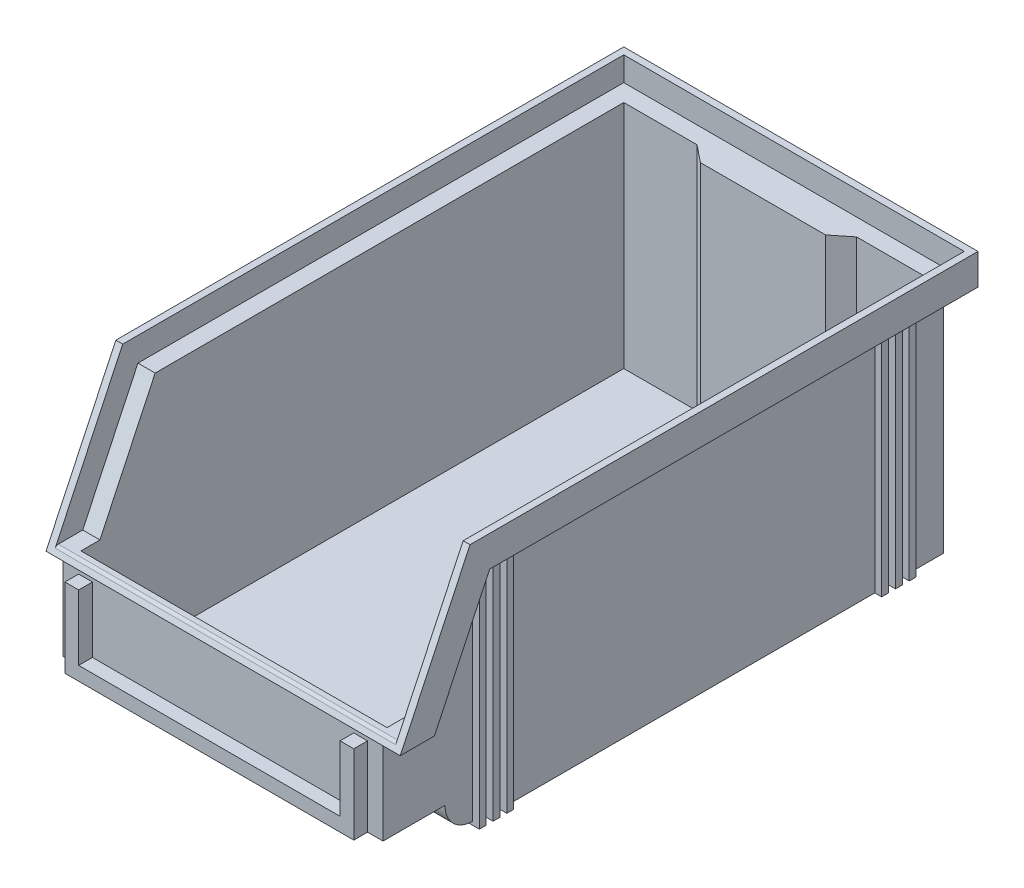
SolidWorks part; units mm, degrees
ref_plane "Front Plane" through (0, 0, 0) normal (0, 0, 1) x (1, 0, 0)
ref_plane "Top Plane" through (0, 0, 0) normal (0, 1, 0) x (1, 0, 0)
ref_plane "Right Plane" through (0, 0, 0) normal (1, 0, 0) x (0, 0, -1)
sketch "Sketch1" plane through (0, 0, 0) normal (0, 1, 0) x (1, 0, 0)
  line L0 (-17.5, 64.5) -> (17.5, 64.5)
  line L1 (-46.5, -68.5) -> (46.5, -68.5)
  line L2 (-46.5, -68.5) -> (-46.5, 68.5)
  line L3 (-46.5, 68.5) -> (46.5, 68.5) construction
  line L4 (46.5, -68.5) -> (46.5, 68.5)
  line L5 (-46.5, -68.5) -> (46.5, 68.5) construction
  line L6 (-46.5, 68.5) -> (46.5, -68.5) construction
  line L7 (-17.5, 64.5) -> (-22.5, 68.5)
  line L8 (17.5, 64.5) -> (22.5, 68.5)
  line L9 (-46.5, 68.5) -> (-22.5, 68.5)
  line L10 (22.5, 68.5) -> (46.5, 68.5)
  point P0 (0, 0)
  point P8 (0, 64.5)
  dimension "D1" = 93
  dimension "D2" = 137
  dimension "D3" = 35
  dimension "D4" = 45
  dimension "D5" = 4
extrude "Boss-Extrude1" add sketch "Sketch1" along normal blind 67
sketch "Sketch2" plane through (0, 67, 0) normal (0, 1, 0) x (1, 0, 0)
  line L0 (-22.5, 68.5) -> (-46.5, 68.5) construction
  line L1 (-51.5, 73.5) -> (51.5, 73.5)
  line L2 (-51.5, 73.5) -> (-51.5, -68.5)
  line L3 (-51.5, -68.5) -> (51.5, -68.5)
  line L4 (51.5, 73.5) -> (51.5, -68.5)
  line L5 (-46.5, 68.5) -> (-46.5, -68.5) construction
  line L6 (46.5, -68.5) -> (46.5, 68.5) construction
  dimension "D1" = 5
  dimension "D2" = 5
  dimension "D3" = 5
extrude "Boss-Extrude2" add sketch "Sketch2" along normal blind 9
sketch "Sketch3" plane through (0, 67, 0) normal (0, -1, 0) x (1, 0, 0)
  line L0 (51.5, -73.5) -> (-51.5, -73.5) construction
  line L2 (45, -73.5) -> (-45, -73.5)
  line L3 (45, -73.5) -> (45, -71.5)
  line L4 (45, -71.5) -> (-45, -71.5)
  line L5 (-45, -73.5) -> (-45, -71.5)
  point P6 (0, -73.5)
  dimension "D1" = 90
  dimension "D2" = 2
extrude "Boss-Extrude3" add sketch "Sketch3" along normal blind 4 contours L3 L2 L5 L4
sketch "Sketch4" plane through (0, 0, 68.5) normal (0, 0, 1) x (1, 0, 0)
  line L0 (-46.5, 67) -> (-46.5, 0) construction
  line L1 (-46.5, 9) -> (46.5, 9)
  line L2 (-46.5, 9) -> (-46.5, 33)
  line L3 (-46.5, 33) -> (46.5, 33)
  line L4 (46.5, 9) -> (46.5, 33)
  line L5 (46.5, 67) -> (46.5, 0) construction
  line L6 (-46.5, 0) -> (46.5, 0) construction
  dimension "D1" = 9
  dimension "D2" = 24
extrude "Boss-Extrude4" add sketch "Sketch4" along normal blind 26
sketch "Sketch5" plane through (-46.5, 0, 0) normal (-1, 0, 0) x (0, 0, 1)
  line L0 (68.5, 67) -> (94.5, 33)
  line L1 (94.5, 33) -> (68.5, 33)
  line L2 (68.5, 33) -> (68.5, 67)
extrude "Boss-Extrude5" add sketch "Sketch5" against normal up to surface (93 mm away) up to face at (46.5, 27.25, 40.75)
sketch "Sketch7" plane through (-51.5, 0, 0) normal (-1, 0, 0) x (0, 0, 1)
  line L0 (68.5, 67) -> (84.5479, 33)
  line L1 (84.5479, 33) -> (94.5, 33)
  line L2 (94.5, 33) -> (74.2042, 76)
  line L3 (74.2042, 76) -> (68.5, 76)
  line L4 (68.5, 76) -> (68.5, 67)
  dimension "D1" = 9
extrude "Boss-Extrude6" add sketch "Sketch7" against normal up to surface (103 mm away) contours L4 L0 L1 L2 L3 up to face at (51.5, 71.5, -2.5)
sketch "Sketch8" plane through (-46.5, 0, 0) normal (-1, 0, 0) x (0, 0, 1)
  line L0 (68.5, 9) -> (68.5, 0) construction
  line L1 (94.5, 9) -> (68.5, 9) construction
  line L2 (76.5, 9) -> (68.5, 9)
  line L3 (68.5, 9) -> (68.5, 1)
  arc A0 (68.5, 1) -> (76.5, 9) centre (68.5, 9) ccw
  dimension "D1" = 8
extrude "Boss-Extrude7" add sketch "Sketch8" against normal up to surface (93 mm away) up to face at (46.5, 27.25, 42.756)
shell "Shell5" thickness 2 removed face at (0, 76, 0.3521)
sketch "Sketch11" plane through (0, 0, 94.5) normal (0, 0, 1) x (1, 0, 0)
  line L0 (51.5, 76) -> (-51.5, 76) construction
  line L1 (-49.5, 35) -> (49.5, 35)
  line L2 (-49.5, 35) -> (-49.5, 76)
  line L3 (-49.5, 76) -> (49.5, 76)
  line L4 (49.5, 35) -> (49.5, 76)
  line L5 (-51.5, 33) -> (-51.5, 76) construction
  line L6 (51.5, 76) -> (51.5, 33) construction
  line L7 (51.5, 33) -> (46.5, 33) construction
  dimension "D1" = 2
  dimension "D2" = 2
  dimension "D3" = 2
extrude "Cut-Extrude1" cut sketch "Sketch11" against normal up to surface (8.6845 mm away) up to face at (-47, 52, 77.7915)
fillet "Fillet2" radius 1 1 edges at (0, 35, 93.556)
sketch "Sketch12" plane through (-46.5, 0, 0) normal (-1, 0, 0) x (0, 0, 1)
  line L0 (-68.5, 0) -> (68.5, 0) construction
  line L1 (-58.5, 0) -> (-56.5, 0)
  line L2 (-58.5, 0) -> (-58.5, 67)
  line L3 (-58.5, 67) -> (-56.5, 67)
  line L4 (-56.5, 0) -> (-56.5, 67)
  line L5 (-68.5, 67) -> (68.5, 67) construction
  line L6 (-73.5, 67) -> (68.5, 67) construction
  line L7 (-54.5, 67) -> (-52.5, 67)
  line L8 (-54.5, 67) -> (-54.5, 0)
  line L9 (-54.5, 0) -> (-52.5, 0)
  line L10 (-52.5, 67) -> (-52.5, 0)
  line L11 (-50.5, 0) -> (-48.5, 0)
  line L12 (-50.5, 0) -> (-50.5, 67)
  line L13 (-50.5, 67) -> (-48.5, 67)
  line L14 (-48.5, 0) -> (-48.5, 67)
  line L15 (58.5, 0) -> (60.5, 0)
  line L16 (58.5, 0) -> (58.5, 67)
  line L17 (58.5, 67) -> (60.5, 67)
  line L18 (60.5, 0) -> (60.5, 67)
  line L19 (-56.5, 0) -> (-54.5, 0) construction
  line L20 (62.5, 67) -> (64.5, 67)
  line L21 (62.5, 67) -> (62.5, 0)
  line L22 (62.5, 0) -> (64.5, 0)
  line L23 (64.5, 67) -> (64.5, 0)
  line L24 (66.5, 0) -> (68.5, 0)
  line L25 (66.5, 0) -> (66.5, 67)
  line L26 (66.5, 67) -> (68.5, 67)
  line L27 (68.5, 0) -> (68.5, 67)
  line L28 (-52.5, 0) -> (-50.5, 0) construction
  line L29 (60.5, 0) -> (62.5, 0) construction
  line L30 (64.5, 0) -> (66.5, 0) construction
  line L31 (-68.5, 67) -> (-68.5, 0) construction
  line L32 (68.5, 1) -> (68.5, 0) construction
  dimension "D1" = 2
  dimension "D2" = 10
  dimension "D3" = 2
extrude "Boss-Extrude8" add sketch "Sketch12" along normal blind 2
mirror "Mirror1" about plane through (0, 0, 0) normal (1, 0, 0) of "Boss-Extrude8"
sketch "Sketch13" plane through (0, 0, 94.5) normal (0, 0, 1) x (1, 0, 0)
  line L0 (46.5, 9) -> (-46.5, 9) construction
  line L1 (-42, 9) -> (-38, 9)
  line L2 (-42, 9) -> (-42, 32)
  line L3 (-42, 32) -> (-38, 32)
  line L4 (-38, 9) -> (-38, 32)
  line L5 (46.5, 33) -> (-46.5, 33) construction
  line L6 (-38, 9) -> (38, 9)
  line L7 (-38, 9) -> (-38, 13)
  line L8 (-38, 13) -> (38, 13)
  line L9 (38, 9) -> (38, 13)
  line L10 (38, 9) -> (42, 9)
  line L11 (38, 9) -> (38, 32)
  line L12 (38, 32) -> (42, 32)
  line L13 (42, 9) -> (42, 32)
  point P14 (0, 13)
  dimension "D1" = 4
  dimension "D2" = 1
  dimension "D3" = 84
extrude "Boss-Extrude9" add sketch "Sketch13" along normal blind 4 contours L5 L4 L3 L2 | L5 L9 L8 L4 | L5 L13 L12 L11 L9 region at (-40, 20.5, 94.5) region at (0, 11, 94.5) region at (40, 20.5, 94.5)
